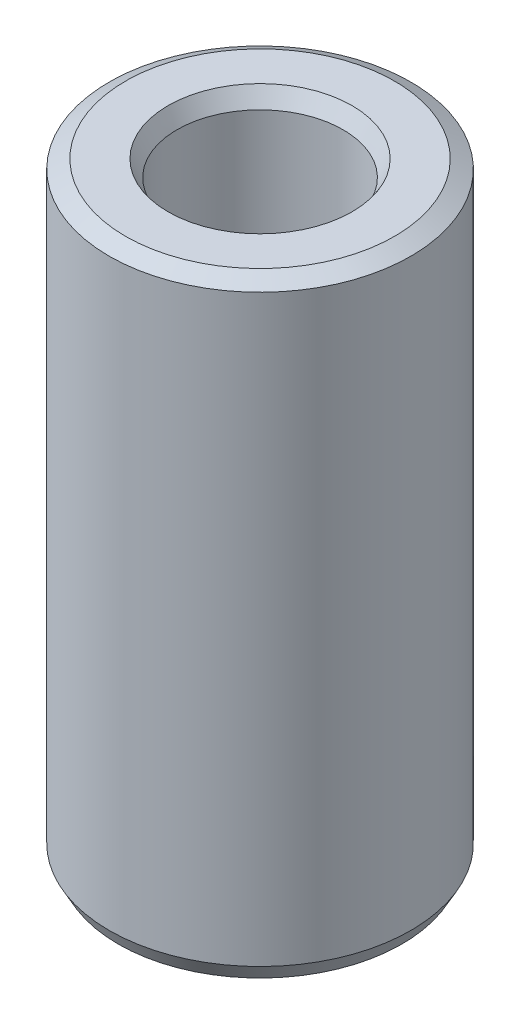
SolidWorks part; units mm, degrees
ref_plane "Front Plane" through (0, 0, 0) normal (0, 0, 1) x (1, 0, 0)
ref_plane "Top Plane" through (0, 0, 0) normal (0, 1, 0) x (1, 0, 0)
ref_plane "Right Plane" through (0, 0, 0) normal (1, 0, 0) x (0, 0, -1)
sketch "Sketch1" plane through (0, 0, 0) normal (0, 1, 0) x (1, 0, 0)
  circle A0 centre (0, 0) radius 35
  dimension "SLEEVE_OD" = 70
extrude "Boss-Extrude1" add sketch "Sketch1" along normal blind 141.3615
sketch "Sketch2" plane through (0, 0, 0) normal (0, 1, 0) x (1, 0, 0)
  circle A0 centre (0, 0) radius 19.2594
  dimension "BORE_D" = 38.5188
extrude "Cut-Extrude1" cut sketch "Sketch2" along normal through all
chamfer "Chamfer1" distance 2.0899 angle 61.152 4 edges at (0, 141.3615, 19.2594) (0, 0, 19.2594) (0, 0, 35) (0, 141.3615, 35) first distance on face at (0, 141.3615, 19.2594) first distance on face at (0, 0, 19.2594) first distance on face at (0, 141.3615, 35)
